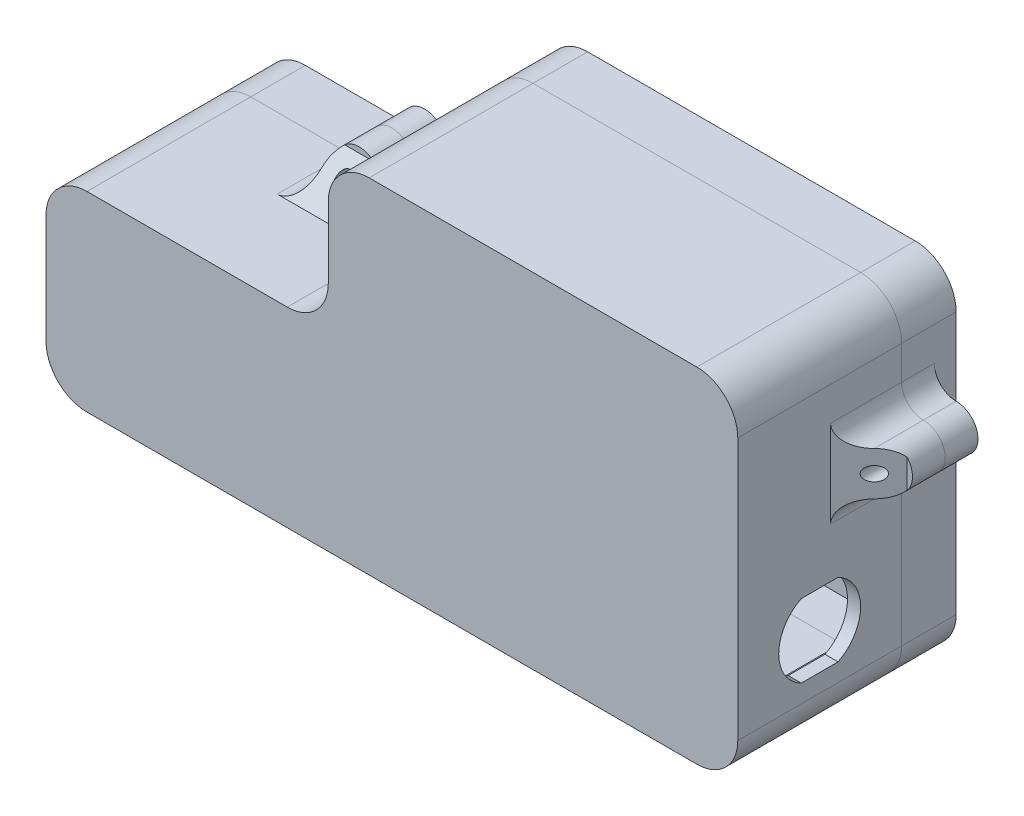
SolidWorks part; units mm, degrees
ref_plane "Front Plane" through (0, 0, 0) normal (0, 0, 1) x (1, 0, 0)
ref_plane "Top Plane" through (0, 0, 0) normal (0, 1, 0) x (1, 0, 0)
ref_plane "Right Plane" through (0, 0, 0) normal (1, 0, 0) x (0, 0, -1)
sketch "Sketch2" plane through (0, 0, 0) normal (0, 0, 1) x (1, 0, 0)
  line L1 (-63.35, 17.5) -> (63.35, 17.5)
  line L2 (-63.35, 17.5) -> (-63.35, -17.5)
  line L3 (-63.35, -17.5) -> (63.35, -17.5)
  line L4 (63.35, 17.5) -> (63.35, -17.5)
  line L5 (63.35, 17.5) -> (-11.65, 17.5)
  line L6 (63.35, 17.5) -> (63.35, 45.5)
  line L7 (63.35, 45.5) -> (-11.65, 45.5)
  line L8 (-11.65, 17.5) -> (-11.65, 45.5)
  line L9 (63.35, 17.5) -> (-11.65, 45.5) construction
  line L10 (63.35, 45.5) -> (-11.65, 17.5) construction
  circle A0 centre (0, 0) radius 7.95
  circle A1 centre (-45.4, 0) radius 7.95
  circle A2 centre (45.4, 0) radius 7.95
  point P12 (63.35, 0)
  point P15 (25.85, 31.5)
  dimension "D1" = 15.9
  dimension "D2" = 29.5
  dimension "D3" = 29.5
  dimension "D8" = 28
  dimension "D6" = 10
  dimension "D5" = 75
  dimension "D4" = 35
  dimension "D7" = 10
extrude "Boss-Extrude1" add sketch "Sketch2" along normal blind 40 contours L8 L1 L6 L7 | L1 L4 L3 L2 region at (25.85, 31.5, 0)
fillet "Fillet1" radius 7.5 6 edges at (-63.35, 17.5, 20) (-63.35, -17.5, 20) (63.35, -17.5, 20) (63.35, 45.5, 20) (-11.65, 45.5, 20) (-11.65, 17.5, 20)
shell "Shell2" thickness 2.4
extrude "Cut-Extrude1" cut sketch "Sketch2<4>" along normal blind 30 contours A2 | A0 | A1 region at (0, 0, 0) region at (-45.4, 0, 0) region at (45.4, 0, 0)
sketch "Sketch2<4>" plane through (0, 0, 0) normal (0, 0, 1) x (1, 0, 0) same geometry as "Sketch2"
ref_plane "Plane1" through (0, 0, 10) normal (0, 0, -1) x (-1, 0, 0)
sketch "Sketch3" plane through (0, 0, 10) normal (0, 0, -1) x (-1, 0, 0)
  line L1 (-55.85, 45.5) -> (4.15, 45.5) construction
  line L2 (38, -17.5) -> (38, 17.5) construction
  line L4 (0, 0) -> (0, -38.9983) construction
  line L5 (55.85, 17.5) -> (19.15, 17.5) construction
  line L6 (38, 17.5) -> (22, 17.5)
  line L7 (0, 45.5) -> (-22, 45.5) construction
  line L8 (-38, 45.5) -> (-55.85, 45.5) construction
  line L9 (-38, 45.5) -> (-22, 45.5)
  line L10 (38, 45.5) -> (22, 45.5)
  line L11 (-63.35, 14) -> (63.35, 14) construction
  line L12 (38, -17.5) -> (22, -17.5)
  line L13 (-38, -17.5) -> (-22, -17.5)
  line L14 (-63.35, 31.829) -> (-63.35, 15.829)
  line L15 (-63.35, -10) -> (-63.35, 38) construction
  arc A10 (-26, 49.5) -> (-34, 49.5) centre (-30, 49.5) ccw
  arc A11 (-26, 49.5) -> (-22, 45.5) centre (-22, 49.5) ccw
  arc A12 (-34, 49.5) -> (-38, 45.5) centre (-38, 49.5) cw
  circle A13 centre (-30, 49.5) radius 1.3
  circle A14 centre (30, 49.5) radius 1.3
  arc A15 (26, 49.5) -> (22, 45.5) centre (22, 49.5) cw
  arc A16 (34, 49.5) -> (38, 45.5) centre (38, 49.5) ccw
  arc A17 (26, 49.5) -> (34, 49.5) centre (30, 49.5) cw
  arc A18 (26, -21.5) -> (34, -21.5) centre (30, -21.5) ccw
  arc A19 (34, -21.5) -> (38, -17.5) centre (38, -21.5) cw
  arc A20 (26, -21.5) -> (22, -17.5) centre (22, -21.5) ccw
  circle A21 centre (30, -21.5) radius 1.3
  arc A22 (-34, -21.5) -> (-38, -17.5) centre (-38, -21.5) ccw
  circle A23 centre (-30, -21.5) radius 1.3
  arc A24 (-26, -21.5) -> (-22, -17.5) centre (-22, -21.5) cw
  arc A25 (-26, -21.5) -> (-34, -21.5) centre (-30, -21.5) cw
  circle A26 centre (30, 21.5) radius 1.3
  arc A27 (26, 21.5) -> (22, 17.5) centre (22, 21.5) cw
  arc A28 (34, 21.5) -> (38, 17.5) centre (38, 21.5) ccw
  arc A29 (26, 21.5) -> (34, 21.5) centre (30, 21.5) cw
  circle A30 centre (-67.35, 23.829) radius 1.3
  arc A31 (-67.35, 19.829) -> (-63.35, 15.829) centre (-67.35, 15.829) cw
  arc A32 (-67.35, 27.829) -> (-63.35, 31.829) centre (-67.35, 31.829) ccw
  arc A33 (-67.35, 19.829) -> (-67.35, 27.829) centre (-67.35, 23.829) cw
  point P0 (0, 45.5)
  point P61 (-63.35, 31.829)
  dimension "D3" = 4
  dimension "D4" = 2.6
  dimension "D5" = 30
extrude "Boss-Extrude2" add sketch "Sketch3" along normal mid plane 12 contours A29 A27 L6 A28 A26 | A33 A31 L14 A32 A30 | A25 A24 L13 A22 A23 | A20 A18 A19 L12 A21 region at (-30, 17.6789, 10) region at (-35.0451, -18.5451, 10) region at (30, -17.6789, 10) region at (63.5289, 23.829, 10)
sketch "Sketch6" plane through (0, 0, 40) normal (0, 0, 1) x (1, 0, 0)
  line L0 (0, 0) -> (0, 12.568) construction
  line L1 (0, 12.568) -> (0, 0) construction
  line L2 (0, 0) -> (-10.24, 0) construction
  circle A0 centre (-58.418, 12.568) radius 2.5
  circle A1 centre (-58.418, 12.568) radius 1.25
  circle A2 centre (58.418, 12.568) radius 1.25
  circle A3 centre (58.418, 12.568) radius 2.5
  circle A4 centre (58.418, -12.568) radius 2.5
  circle A5 centre (58.418, -12.568) radius 1.25
  circle A6 centre (-58.418, -12.568) radius 1.25
  circle A7 centre (-58.418, -12.568) radius 2.5
  dimension "D1" = 2.5
  dimension "D2" = 5
extrude "Boss-Extrude3" add sketch "Sketch6" against normal blind 40
extrude "Cut-Extrude3" cut sketch "Sketch6<2>" against normal through all from offset 10 contours A6 | A1 | A2 | A5 offset against normal yes
sketch "Sketch6<2>" plane through (0, 0, 40) normal (0, 0, 1) x (1, 0, 0) same geometry as "Sketch6"
split "Split1" trim tools "Plane1" bodies to split 109 resulting bodies 104 105
sketch "Sketch5" plane through (-63.35, 0, 0) normal (-1, 0, 0) x (0, 0, 1)
  line L0 (10, 10) -> (40, -10) construction
  line L1 (10, 34.65) -> (10, -34.65) construction
  line L2 (40, 10) -> (10, 10) construction
  line L6 (21.6295, -6.7) -> (28.3705, -6.7)
  line L8 (28.3705, 6.7) -> (21.6295, 6.7)
  arc A0 (21.6295, 6.7) -> (21.6295, -6.7) centre (25, 0) ccw
  arc A1 (28.3705, -6.7) -> (28.3705, 6.7) centre (25, 0) ccw
  dimension "D1" = 15
  dimension "D2" = 13.4
extrude "Cut-Extrude2" cut sketch "Sketch5" against normal through all both and the other way through all contours L8 A0 L6 A1
chamfer "Chamfer1" distance 7 angle 45 4 edges at (-30, -17.5, 16) (30, -17.5, 16) (63.35, 23.829, 16) (-30, 17.5, 16)
sketch "Sketch7" plane through (0, 0, 0) normal (0, 0, -1) x (-1, 0, 0)
  circle A0 centre (45.4, 0) radius 10
  circle A1 centre (45.4, 0) radius 7.95
  circle A2 centre (0, 0) radius 7.95
  circle A3 centre (0, 0) radius 10
  circle A4 centre (-45.4, 0) radius 10
  circle A5 centre (-45.4, 0) radius 7.95
  circle A6 centre (-45.4, 0) radius 7.95 construction
  circle A7 centre (0, 0) radius 7.95 construction
  dimension "D1" = 20
extrude "Boss-Extrude4" add sketch "Sketch7" along normal blind 2
sketch "Sketch8" plane through (0, 0, 2.4) normal (0, 0, -1) x (-1, 0, 0)
  line L1 (-3.4697, 16.1541) -> (-50.9697, 16.1541) construction
  line L2 (-3.4697, 16.1541) -> (-3.4697, 38.1541) construction
  line L3 (-3.4697, 38.1541) -> (-50.9697, 38.1541) construction
  line L4 (-50.9697, 16.1541) -> (-50.9697, 38.1541) construction
  line L5 (-3.4697, 16.1541) -> (-50.9697, 38.1541) construction
  line L6 (-3.4697, 38.1541) -> (-50.9697, 16.1541) construction
  circle A0 centre (-3.4697, 16.1541) radius 1.25
  circle A1 centre (-50.9697, 16.1541) radius 1.25
  circle A2 centre (-50.9697, 38.1541) radius 1.25
  circle A3 centre (-3.4697, 38.1541) radius 1.25
  circle A4 centre (-3.4697, 38.1541) radius 4.25
  circle A5 centre (-3.4697, 16.1541) radius 4.25
  circle A6 centre (-50.9697, 16.1541) radius 4.25
  circle A7 centre (-50.9697, 38.1541) radius 4.25
  point P4 (-27.2197, 27.1541)
  dimension "D3" = 2.5
  dimension "D1" = 22
  dimension "D2" = 47.5
extrude "Boss-Extrude5" add sketch "Sketch8" against normal blind 5
